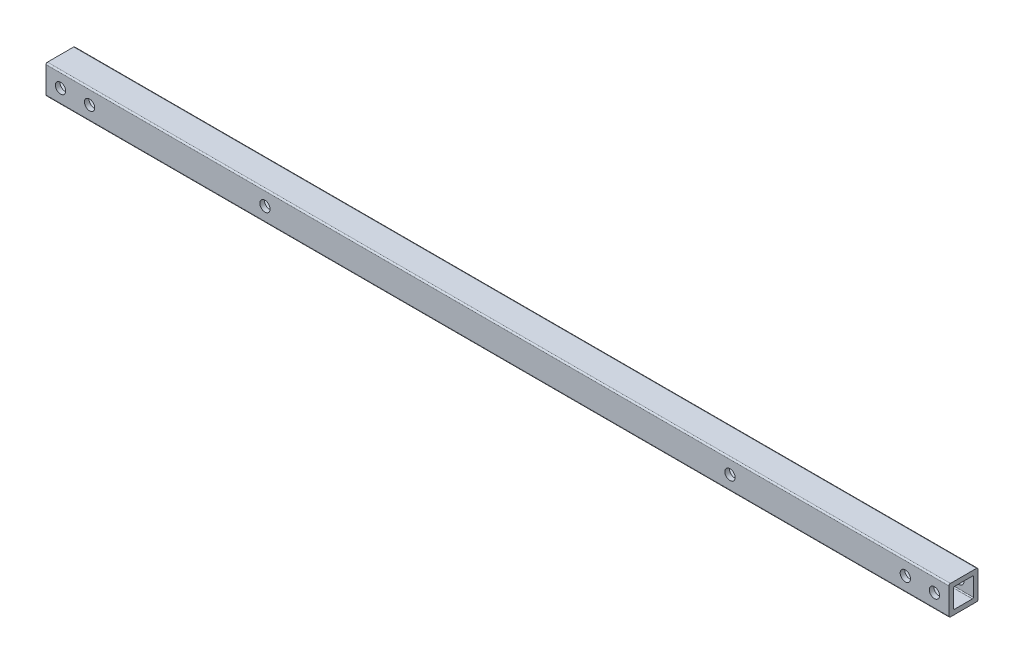
SolidWorks part; units mm, degrees
ref_plane "Front" through (0, 0, 0) normal (0, 0, 1) x (1, 0, 0)
ref_plane "Top" through (0, 0, 0) normal (0, 1, 0) x (1, 0, 0)
ref_plane "Right" through (0, 0, 0) normal (1, 0, 0) x (0, 0, -1)
sketch "Sketch1" plane through (0, 0, 0) normal (1, 0, 0) x (0, 0, -1)
  line L0 (-6.477, 0) -> (-9.525, 0) construction
  line L1 (8.5725, -9.525) -> (-8.5725, -9.525) construction
  line L2 (9.525, -8.5725) -> (9.525, 8.5725) construction
  line L3 (8.5725, 9.525) -> (-8.5725, 9.525) construction
  line L4 (-9.525, -8.5725) -> (-9.525, 8.5725) construction
  line L5 (9.525, -9.525) -> (-9.525, 9.525) construction
  line L6 (9.525, 9.525) -> (-9.525, -9.525) construction
  line L7 (5.8293, 6.477) -> (-5.8293, 6.477) construction
  line L8 (6.477, 5.8293) -> (6.477, -5.8293) construction
  line L9 (5.8293, -6.477) -> (-5.8293, -6.477) construction
  line L10 (-6.477, 5.8293) -> (-6.477, -5.8293) construction
  line L11 (6.477, 6.477) -> (-6.477, -6.477) construction
  line L12 (6.477, -6.477) -> (-6.477, 6.477) construction
  line L13 (0, -6.477) -> (0, -9.525) construction
  line L14 (6.477, -5.8293) -> (6.477, -9.525) construction
  line L15 (6.477, 0) -> (9.525, 0) construction
  line L16 (6.477, -9.525) -> (9.525, -9.525) construction
  arc A0 (-5.8293, -6.477) -> (-6.477, -5.8293) centre (-5.8293, -5.8293) cw construction
  arc A1 (6.477, -5.8293) -> (5.8293, -6.477) centre (5.8293, -5.8293) cw construction
  arc A2 (5.8293, 6.477) -> (6.477, 5.8293) centre (5.8293, 5.8293) cw construction
  arc A3 (-5.8293, 6.477) -> (-6.477, 5.8293) centre (-5.8293, 5.8293) ccw construction
  arc A4 (8.5725, -9.525) -> (9.525, -8.5725) centre (8.5725, -8.5725) ccw construction
  arc A5 (9.525, 8.5725) -> (8.5725, 9.525) centre (8.5725, 8.5725) ccw construction
  arc A6 (-8.5725, 9.525) -> (-9.525, 8.5725) centre (-8.5725, 8.5725) ccw construction
  arc A7 (-8.5725, -9.525) -> (-9.525, -8.5725) centre (-8.5725, -8.5725) cw construction
  point P0 (0, 0)
  point P6 (0, 0)
  dimension "D2" = 0.6477
  dimension "D3" = 0.9525
  dimension "Outside Width" = 19.05
  dimension "Ouside Height" = 19.05
  dimension "Inside Height" = 12.954
  dimension "Wall Thickness" = 3.048
sketch "Sketch2" plane through (0, 0, 0) normal (0, 0, 1) x (1, 0, 0)
  line L0 (-457.2, 0) -> (457.2, 0) construction
  point P3 (-441.198, 0)
  point P4 (441.198, 0)
  dimension "Length" = 914.4
  dimension "D1" = 16.002
  dimension "D2" = 16.002
sketch "Sketch4" plane through (0, 0, 0) normal (1, 0, 0) x (0, 0, -1)
  line L8 (9.525, -8.5725) -> (9.525, 8.5725)
  line L9 (8.5725, 9.525) -> (-8.5725, 9.525)
  line L10 (-9.525, -8.5725) -> (-9.525, 8.5725)
  line L11 (8.5725, -9.525) -> (-8.5725, -9.525)
  line L12 (6.477, 5.8293) -> (6.477, -5.8293)
  line L13 (5.8293, -6.477) -> (-5.8293, -6.477)
  line L14 (-6.477, 5.8293) -> (-6.477, -5.8293)
  line L15 (5.8293, 6.477) -> (-5.8293, 6.477)
  arc A8 (9.525, 8.5725) -> (8.5725, 9.525) centre (8.5725, 8.5725) ccw
  arc A9 (-8.5725, 9.525) -> (-9.525, 8.5725) centre (-8.5725, 8.5725) ccw
  arc A10 (-9.525, -8.5725) -> (-8.5725, -9.525) centre (-8.5725, -8.5725) ccw
  arc A11 (8.5725, -9.525) -> (9.525, -8.5725) centre (8.5725, -8.5725) ccw
  arc A12 (5.8293, -6.477) -> (6.477, -5.8293) centre (5.8293, -5.8293) ccw
  arc A13 (-6.477, -5.8293) -> (-5.8293, -6.477) centre (-5.8293, -5.8293) ccw
  arc A14 (-5.8293, 6.477) -> (-6.477, 5.8293) centre (-5.8293, 5.8293) ccw
  arc A15 (6.477, 5.8293) -> (5.8293, 6.477) centre (5.8293, 5.8293) ccw
extrude "Boss-Extrude1" add sketch "Sketch4" along normal mid plane 591.82
hole_wizard "1/4 Clearance Hole1" positions "Sketch5" profile "Sketch6" hole size "1/4" standard "ANSI Inch"
sketch "Sketch5" plane through (348.7325, 47.625, -9.525) normal (0, 0, -1) x (-1, 0, 0)
  line L0 (30.5975, -47.625) -> (81.3975, -47.625) construction
  line L1 (196.3325, 47.625) -> (196.3325, -47.625) construction
  point P0 (30.5975, -47.625)
  point P3 (62.3475, -47.625)
  point P5 (81.3975, -47.625)
  point P15 (196.3325, -47.625)
sketch "Sketch6" plane through (318.135, 0, -9.525) normal (1, 0, 0) x (0, 1, 0)
  line L0 (0, 0) -> (0, 21.0798)
  line L1 (0, 21.0798) -> (3.3782, 19.05)
  line L2 (3.3782, 19.05) -> (3.3782, 0)
  line L3 (3.3782, 0) -> (0, 0)
  line L4 (0, 21.0798) -> (-3.3782, 19.05) construction
  line L5 (0, -6.35) -> (0, 107.95) construction
  dimension "Hole Dia." = 6.7564
  dimension "Hole Depth" = 19.05
  dimension "Drill Angle" = 118
mirror "Mirror2" about plane through (0, 0, 0) normal (1, 0, 0) of "1/4 Clearance Hole1"
equation "\"D3@Sketch1\"=\"Outside Width@Sketch1\"*.05"
equation "\"D2@Sketch1\" = \"Inside Height@Sketch1\" * .05"
equation "\"D1@Sketch2\"=\"Outside Width@Sketch1\"-\"Wall Thickness@Sketch1\""
equation "\"D2@Sketch2\"=\"D1@Sketch2\""
